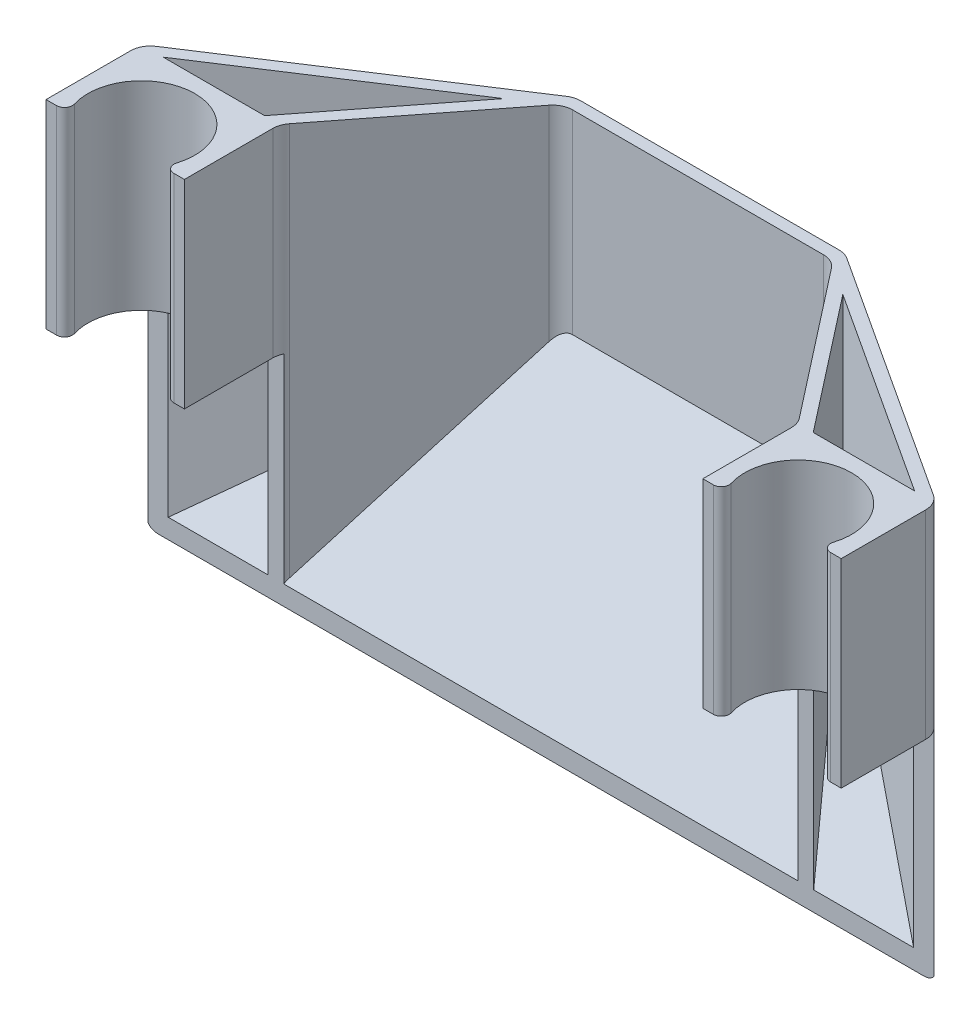
SolidWorks part; units mm, degrees
ref_plane "Front Plane" through (0, 0, 0) normal (0, 0, 1) x (1, 0, 0)
ref_plane "Top Plane" through (0, 0, 0) normal (0, 1, 0) x (1, 0, 0)
ref_plane "Right Plane" through (0, 0, 0) normal (1, 0, 0) x (0, 0, -1)
sketch "Sketch1" plane through (0, 0, 0) normal (0, 1, 0) x (1, 0, 0)
  line L0 (0, 0) -> (-34, 0)
  line L1 (-34, 0) -> (-100, -43)
  line L2 (-100, -43) -> (-100, -66.97)
  line L3 (-100, -66.97) -> (-97.3586, -66.97)
  line L4 (-67.8414, -66.97) -> (-65.2, -66.97)
  line L5 (-65.2, -66.97) -> (-65.2, -43)
  line L6 (-69.0047, -43) -> (-94.5043, -43)
  line L7 (-94.5043, -43) -> (-42.6567, -9.2205)
  line L8 (-34, -3) -> (0, -3)
  line L9 (0, -3) -> (0, 0)
  line L10 (-69.0047, -43) -> (-42.6567, -9.2205)
  line L11 (-34, -3) -> (-65.2, -43)
  arc A0 (-95.4481, -64.3784) -> (-69.7519, -64.3784) centre (-82.6, -60.4) cw
  arc A1 (-67.8414, -66.97) -> (-69.7519, -64.3784) centre (-67.8414, -64.97) cw
  arc A2 (-95.4481, -64.3784) -> (-97.3586, -66.97) centre (-97.3586, -64.97) cw
  dimension "D3" = 13.45
  dimension "D11" = 2
  dimension "D1" = 100
  dimension "D2" = 34.8
  dimension "D4" = 17.4
  dimension "D5" = 23.97
  dimension "D6" = 3
  dimension "D7" = 43
  dimension "D8" = 3
  dimension "D9" = 3
  dimension "D10" = 3
  dimension "D12" = 66
extrude "Boss-Extrude1" add sketch "Sketch1" along normal blind 50
mirror "Mirror1" about plane through (0, 50, 3) normal (-1, 0, 0) of "Boss-Extrude1"
fillet "Fillet1" radius 5 8 edges at (-100, 25, 43) (-34, 25, 0) (34, 25, 0) (100, 25, 43) (65.2, 25, 43) (34, 25, 3) (-34, 25, 3) (-65.2, 25, 43)
sketch "Sketch2" plane through (0, 0, 0) normal (0, 1, 0) x (1, 0, 0)
  line L1 (-42.6567, -9.2205) -> (-94.5043, -43) construction
  line L2 (-69.0047, -43) -> (-42.6567, -9.2205) construction
  line L4 (42.6567, -9.2205) -> (94.5043, -43) construction
  line L5 (69.0047, -43) -> (42.6567, -9.2205) construction
  line L7 (-42.6567, -9.2205) -> (-93.7368, -42.5)
  line L8 (-68.6147, -42.5) -> (-42.6567, -9.2205)
  line L10 (42.6567, -9.2205) -> (93.7368, -42.5)
  line L11 (68.6147, -42.5) -> (42.6567, -9.2205)
  line L12 (98.8335, -42.5) -> (93.7368, -42.5)
  line L13 (-64.6804, -42.5) -> (-68.6147, -42.5)
  line L14 (-93.7368, -42.5) -> (-98.8335, -42.5)
  line L15 (68.6147, -42.5) -> (64.6804, -42.5)
  line L16 (-94.5043, -43) -> (-69.0047, -43) construction
  line L17 (94.5043, -43) -> (69.0047, -43) construction
  line L20 (-100, -45.71) -> (-100, -66.97)
  line L21 (-35.2443, -0.8107) -> (-97.7294, -41.5207)
  line L22 (32.5149, 0) -> (-32.5149, 0)
  line L23 (97.7294, -41.5207) -> (35.2443, -0.8107)
  line L24 (100, -66.97) -> (100, -45.71)
  line L25 (97.3586, -66.97) -> (100, -66.97)
  line L26 (65.2, -66.97) -> (67.8414, -66.97)
  line L27 (65.2, -44.7194) -> (65.2, -66.97)
  line L28 (35.5014, -4.9248) -> (64.1425, -41.6442)
  line L29 (-31.5589, -3) -> (31.5589, -3)
  line L30 (-64.1425, -41.6442) -> (-35.5014, -4.9248)
  line L31 (-65.2, -66.97) -> (-65.2, -44.7194)
  line L32 (-67.8414, -66.97) -> (-65.2, -66.97)
  line L33 (-100, -66.97) -> (-97.3586, -66.97)
  line L35 (-35.2443, -0.8107) -> (-97.7294, -41.5207)
  line L36 (32.5149, 0) -> (-32.5149, 0)
  line L37 (97.7294, -41.5207) -> (35.2443, -0.8107)
  line L42 (35.5014, -4.9248) -> (64.1425, -41.6442)
  line L43 (-31.5589, -3) -> (31.5589, -3)
  line L44 (-64.1425, -41.6442) -> (-35.5014, -4.9248)
  arc A22 (-97.7294, -41.5207) -> (-100, -45.71) centre (-95, -45.71) ccw
  arc A23 (-32.5149, 0) -> (-35.2443, -0.8107) centre (-32.5149, -5) ccw
  arc A24 (35.2443, -0.8107) -> (32.5149, 0) centre (32.5149, -5) ccw
  arc A25 (100, -45.71) -> (97.7294, -41.5207) centre (95, -45.71) ccw
  arc A26 (95.4481, -64.3784) -> (97.3586, -66.97) centre (97.3586, -64.97) ccw
  arc A27 (95.4481, -64.3784) -> (69.7519, -64.3784) centre (82.6, -60.4) ccw
  arc A28 (67.8414, -66.97) -> (69.7519, -64.3784) centre (67.8414, -64.97) ccw
  arc A29 (65.2, -44.7194) -> (64.1425, -41.6442) centre (60.2, -44.7194) ccw
  arc A30 (35.5014, -4.9248) -> (31.5589, -3) centre (31.5589, -8) ccw
  arc A31 (-31.5589, -3) -> (-35.5014, -4.9248) centre (-31.5589, -8) ccw
  arc A32 (-64.1425, -41.6442) -> (-65.2, -44.7194) centre (-60.2, -44.7194) ccw
  arc A33 (-69.7519, -64.3784) -> (-67.8414, -66.97) centre (-67.8414, -64.97) ccw
  arc A34 (-69.7519, -64.3784) -> (-95.4481, -64.3784) centre (-82.6, -60.4) ccw
  arc A35 (-97.3586, -66.97) -> (-95.4481, -64.3784) centre (-97.3586, -64.97) ccw
  arc A36 (-97.7294, -41.5207) -> (-98.8335, -42.5) centre (-95, -45.71) ccw
  arc A37 (-32.5149, 0) -> (-35.2443, -0.8107) centre (-32.5149, -5) ccw
  arc A38 (35.2443, -0.8107) -> (32.5149, 0) centre (32.5149, -5) ccw
  arc A39 (98.8335, -42.5) -> (97.7294, -41.5207) centre (95, -45.71) ccw
  arc A43 (64.6804, -42.5) -> (64.1425, -41.6442) centre (60.2, -44.7194) ccw
  arc A44 (35.5014, -4.9248) -> (31.5589, -3) centre (31.5589, -8) ccw
  arc A45 (-31.5589, -3) -> (-35.5014, -4.9248) centre (-31.5589, -8) ccw
  arc A46 (-64.1425, -41.6442) -> (-64.6804, -42.5) centre (-60.2, -44.7194) ccw
  dimension "D2" = 0.5
  dimension "D3" = 0.5
  dimension "D1" = 0
extrude "Boss-Extrude2" add sketch "Sketch2" against normal blind 55
sketch "Sketch3" plane through (0, 0, 0) normal (1, 0, 0) x (0, 0, -1)
  line L0 (0, 0) -> (-42.5, -55)
  line L1 (-42.5, -55) -> (0, -55)
  line L2 (0, -55) -> (0, 0)
extrude "Cut-Extrude1" cut sketch "Sketch3" along normal mid plane 210
sketch "Sketch4" plane through (0, 0, 0) normal (0, -0.6114, -0.7913) x (-1, 0, 0)
  line L0 (-97.7294, -67.9055) -> (-35.2443, -1.3258) construction
  line L1 (-32.5149, 0) -> (32.5149, 0) construction
  line L2 (97.7294, -67.9055) -> (35.2443, -1.3258) construction
  line L3 (-97.7294, -67.9055) -> (-35.2443, -1.3258)
  line L4 (-32.5149, 0) -> (32.5149, 0)
  line L5 (97.7294, -67.9055) -> (35.2443, -1.3258)
  line L6 (98.8335, -69.5072) -> (-98.8335, -69.5072)
  ellipse E0 centre (-95, -74.757) end of major axis (-95, -82.9343) minor radius 5 (-97.7294, -67.9055) -> (-98.8335, -69.5072) ccw construction
  ellipse E1 centre (-32.5149, -8.1773) end of major axis (-32.5149, 0) minor radius 5 (-32.5149, 0) -> (-35.2443, -1.3258) ccw construction
  ellipse E2 centre (32.5149, -8.1773) end of major axis (32.5149, -16.3546) minor radius 5 (35.2443, -1.3258) -> (32.5149, 0) ccw construction
  ellipse E3 centre (95, -74.757) end of major axis (95, -82.9343) minor radius 5 (98.8335, -69.5072) -> (97.7294, -67.9055) ccw construction
  ellipse E4 centre (-95, -74.757) end of major axis (-95, -82.9343) minor radius 5 (-97.7294, -67.9055) -> (-98.8335, -69.5072) ccw
  ellipse E5 centre (-32.5149, -8.1773) end of major axis (-32.5149, 0) minor radius 5 (-32.5149, 0) -> (-35.2443, -1.3258) ccw
  ellipse E6 centre (32.5149, -8.1773) end of major axis (32.5149, -16.3546) minor radius 5 (35.2443, -1.3258) -> (32.5149, 0) ccw
  ellipse E7 centre (95, -74.757) end of major axis (95, -82.9343) minor radius 5 (98.8335, -69.5072) -> (97.7294, -67.9055) ccw
extrude "Boss-Extrude3" add sketch "Sketch4" against normal blind 3
sketch "Sketch5" plane through (0, 0, 0) normal (1, 0, 0) x (0, 0, -1)
  line L1 (-42.5, -55) -> (-45.2812, -55)
  line L2 (-42.5, -55) -> (-42.5, -49.9399)
  line L3 (-42.5, -49.9399) -> (-45.2812, -49.9399)
  line L4 (-45.2812, -55) -> (-45.2812, -49.9399)
extrude "Cut-Extrude2" cut sketch "Sketch5" against normal mid plane 213
fillet "Fillet2" radius 5 3 edges at (0, 0, 0) (-33.9385, -0.2678, 0.207) (-66.4869, -27.3909, 21.1657)
